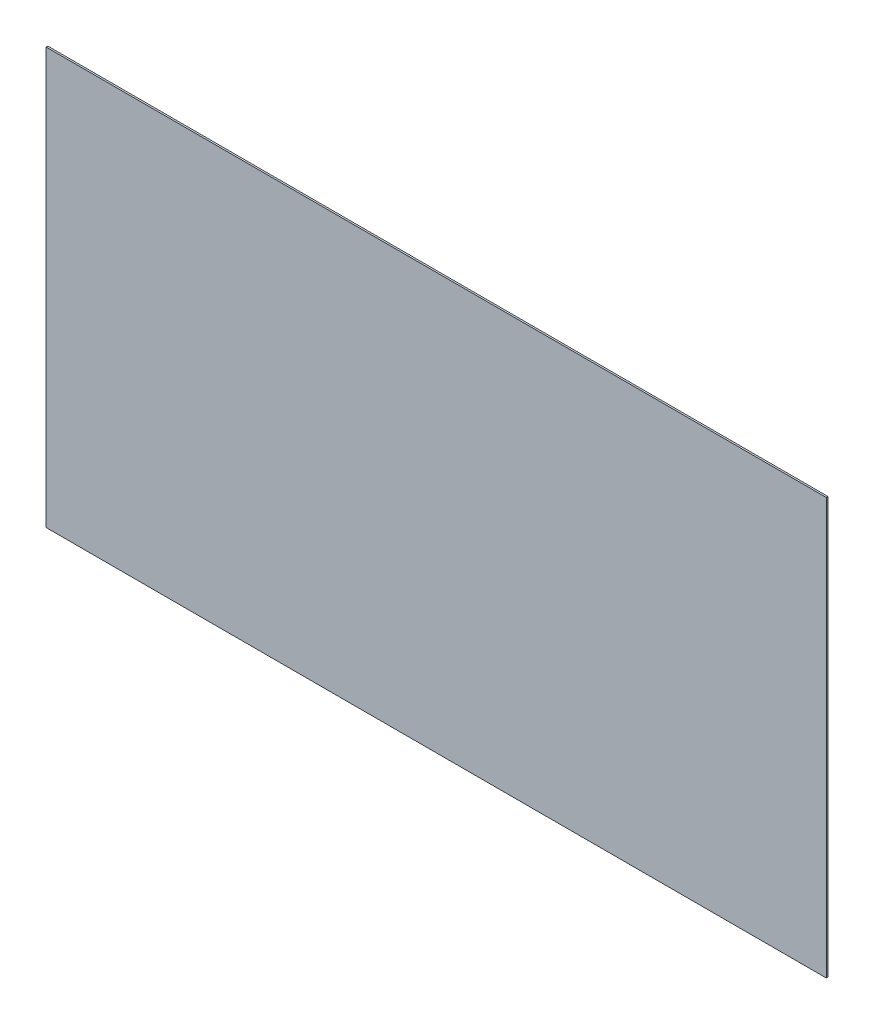
SolidWorks part; units mm, degrees
material "1345 Alloy"
ref_plane "Front Plane" through (0, 0, 0) normal (0, 0, 1) x (1, 0, 0)
ref_plane "Top Plane" through (0, 0, 0) normal (0, 1, 0) x (1, 0, 0)
ref_plane "Right Plane" through (0, 0, 0) normal (1, 0, 0) x (0, 0, -1)
sketch "Sketch1" plane through (0, 0, 0) normal (0, 0, 1) x (1, 0, 0)
  line L1 (-225, 120) -> (225, 120)
  line L2 (-225, 120) -> (-225, -120)
  line L3 (-225, -120) -> (225, -120)
  line L4 (225, 120) -> (225, -120)
  line L5 (-225, 120) -> (225, -120) construction
  line L6 (-225, -120) -> (225, 120) construction
  point P0 (0, 0)
  dimension "D1" = 450
  dimension "D2" = 240
extrude "Boss-Extrude1" add sketch "Sketch1" along normal blind 1
